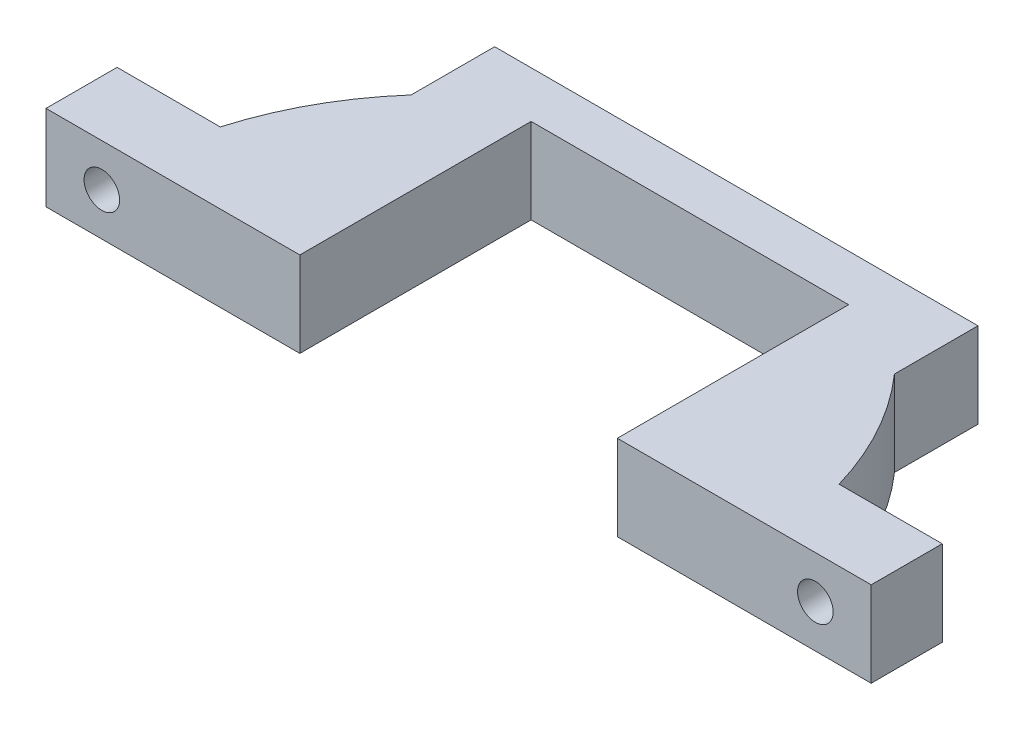
SolidWorks part; units mm, degrees
ref_plane "Alzado" through (0, 0, 0) normal (0, 0, 1) x (1, 0, 0)
ref_plane "Planta" through (0, 0, 0) normal (0, 1, 0) x (1, 0, 0)
ref_plane "Vista lateral" through (0, 0, 0) normal (1, 0, 0) x (0, 0, -1)
sketch "Croquis1" plane through (0, 0, 0) normal (0, 1, 0) x (1, 0, 0)
  line L0 (0, 0) -> (49.0196, 0) construction
  line L1 (0, 0) -> (0, 37.1025) construction
  line L2 (-25.5343, 2) -> (25.5343, 2) construction
  line L3 (25.5343, 2) -> (43.5343, 2)
  line L4 (43.5343, 2) -> (43.5343, 9.5)
  line L5 (43.5343, 9.5) -> (32.6458, 9.5)
  line L6 (-43.5343, 2) -> (-43.5343, 9.5)
  line L7 (-43.5343, 9.5) -> (-32.6458, 9.5)
  line L8 (-25.5343, 2) -> (-43.5343, 2)
  line L9 (-16.75, 26.4024) -> (-16.75, 31.3049) construction
  line L10 (-25.5343, 2) -> (25.5343, 2)
  line L11 (16.75, -7.0976) -> (-16.75, -7.0976)
  line L12 (16.75, -7.0976) -> (16.75, 26.4024)
  line L13 (16.75, 26.4024) -> (-16.75, 26.4024)
  line L14 (-16.75, -7.0976) -> (-16.75, 26.4024)
  line L15 (16.75, -7.0976) -> (-16.75, 26.4024) construction
  line L16 (16.75, 26.4024) -> (-16.75, -7.0976) construction
  line L17 (25.5, 31.3049) -> (-25.5, 31.3049)
  line L19 (22.0343, -9.0572) -> (-25.5, 31.3049) construction
  line L20 (25.5, 31.3049) -> (-22.0343, -9.0572) construction
  line L21 (-17.8885, -12) -> (-20, -12) construction
  line L22 (20, -12) -> (17.8885, -12) construction
  line L23 (25.5343, 2) -> (43.5343, 2)
  line L24 (-17.8885, -12) -> (17.8885, -12) construction
  line L25 (-16.75, -7.0976) -> (-16.75, -12) construction
  line L26 (-25.5, 22.4889) -> (-25.5, 31.3049)
  line L27 (25.5, 22.4889) -> (25.5, 31.3049)
  arc A0 (-25.5, 22.4889) -> (-32.6458, 9.5) centre (0, 0) ccw
  arc A1 (-25.5343, 2) -> (-20, -12) centre (0, 4) ccw construction
  arc A2 (32.6458, 9.5) -> (25.5, 22.4889) centre (0, 0) ccw
  arc A3 (-17.8885, -12) -> (17.8885, -12) centre (0, 4) ccw construction
  arc A4 (20, -12) -> (25.5343, 2) centre (0, 4) ccw construction
  point P12 (0, 9.6524)
  point P14 (0, 0)
  point P15 (0, 9.6524)
  dimension "D1" = 33.5
  dimension "D2" = 51
  dimension "D3" = 34
  dimension "D4" = 29.3049
  dimension "D5" = 2
  dimension "D7" = 7.5
extrude "Saliente-Extruir1" add sketch "Croquis1" along normal blind 9 contours L11 L12 | L5 A2 L3 L4 | A0 L7 L6 L8 region at (21.1421, 0, -2.9187)
sketch "Croquis2" plane through (0, 0, -9.5) normal (0, 0, -1) x (-1, 0, 0)
  line L0 (-32.6458, 9) -> (-32.6458, 0) construction
  line L1 (-32.6458, 9) -> (-32.6458, 0) construction
  line L2 (0, 0) -> (0, 9) construction
  circle A0 centre (-37.645, 4.5) radius 3.5
  circle A1 centre (-37.645, 4.5) radius 1.875
  circle A2 centre (37.645, 4.5) radius 1.875
  circle A3 centre (37.645, 4.5) radius 3.5
  point P10 (-32.6458, 4.5)
  dimension "D1" = 3.75
  dimension "D2" = 7
  dimension "D3" = 37.645
  dimension "D4" = 32.6458
extrude "Cortar-Extruir1" cut sketch "Croquis2" against normal through all contours A2 | A1 region at (-37.645, 4.5, -9.5)
extrude "Cortar-Extruir2" cut sketch "Croquis2<3>" against normal blind 2.8
sketch "Croquis2<3>" plane through (0, 0, -9.5) normal (0, 0, -1) x (-1, 0, 0) same geometry as "Croquis2"
sketch "Croquis3" plane through (0, 0, -31.3049) normal (0, 0, -1) x (-1, 0, 0)
  line L0 (-25.5, 9) -> (-25.5, 0) construction
  line L1 (-25.5, 0) -> (25.5, 0) construction
  circle A0 centre (7.25, 4.5) radius 1.875
  circle A1 centre (-7.25, 4.5) radius 1.875
  point P4 (0, 0)
  point P5 (0, 0)
  point P8 (-25.5, 4.5)
  point P11 (0, 0)
  dimension "D1" = 14.5
  dimension "D2" = 3.75
  dimension "D3" = 7.25
extrude "Cortar-Extruir3" [suppressed] cut sketch "Croquis3" against normal blind 10
